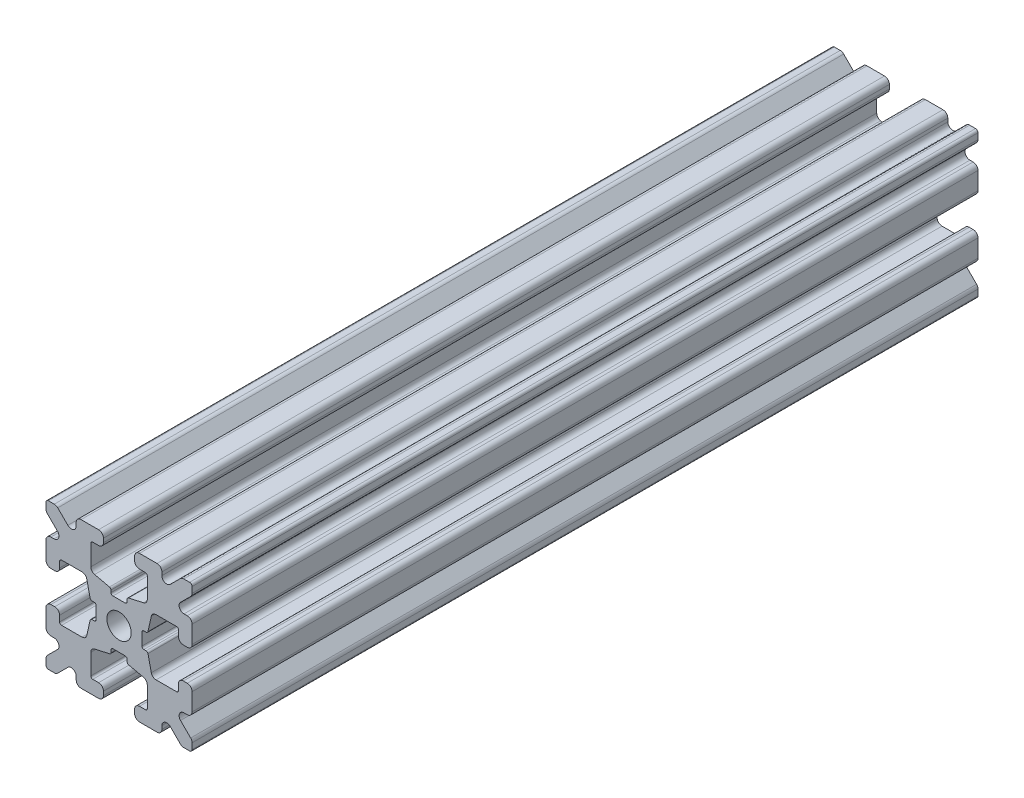
SolidWorks part; units mm, degrees
ref_plane "Front Plane" through (0, 0, 0) normal (0, 0, 1) x (1, 0, 0)
ref_plane "Top Plane" through (0, 0, 0) normal (0, 1, 0) x (1, 0, 0)
ref_plane "Right Plane" through (0, 0, 0) normal (1, 0, 0) x (0, 0, -1)
sketch "Sketch1" plane through (0, 0, 0) normal (0, 0, 1) x (1, 0, 0)
  line L1 (-7.5, -7.5) -> (7.5, -7.5)
  line L2 (-7.5, -7.5) -> (-7.5, 7.5)
  line L3 (-7.5, 7.5) -> (7.5, 7.5)
  line L4 (7.5, -7.5) -> (7.5, 7.5)
  line L5 (-7.5, -7.5) -> (7.5, 7.5) construction
  line L6 (-7.5, 7.5) -> (7.5, -7.5) construction
  circle A0 centre (0, 0) radius 1.25
  point P0 (0, 0)
  dimension "D2" = 2.5
  dimension "D1" = 15
extrude "Boss-Extrude1" add sketch "Sketch1" along normal mid plane 80.7
fillet "Fillet1" radius 0.25 4 edges at (7.5, -7.5, 0) (-7.5, -7.5, 0) (7.5, 7.5, 0) (-7.5, 7.5, 0)
sketch "Sketch2" plane through (0, 0, 40.35) normal (0, 0, 1) x (1, 0, 0)
  line L0 (-7.5, 7.25) -> (-7.5, -7.25) construction
  line L1 (-7.5, 1.6) -> (-6.1, 1.6)
  line L2 (-7.5, 1.6) -> (-7.5, -1.6)
  line L3 (-7.5, -1.6) -> (-6.1, -1.6)
  line L4 (-6.1, 1.6) -> (-6.1, 2.9)
  line L5 (0, 0) -> (-12.1036, 0) construction
  line L6 (-6.1, -2.9) -> (-3.4, -2.9)
  line L7 (0, 0) -> (-7.25, 7.25) construction
  line L8 (-6.1, 2.9) -> (-3.4, 2.9)
  line L9 (-3.4, -2.9) -> (-3.4, 2.9)
  line L10 (55, 0) -> (-55, 0) construction
  line L11 (-6.1, -2.9) -> (-6.1, -1.6)
  line L12 (2.9, 6.1) -> (1.6, 6.1)
  line L13 (2.9, 3.4) -> (-2.9, 3.4)
  line L14 (-2.9, 6.1) -> (-2.9, 3.4)
  line L15 (2.9, 6.1) -> (2.9, 3.4)
  line L16 (-1.6, 6.1) -> (-2.9, 6.1)
  line L17 (1.6, 7.5) -> (1.6, 6.1)
  line L18 (-1.6, 7.5) -> (1.6, 7.5)
  line L19 (-1.6, 7.5) -> (-1.6, 6.1)
  line L20 (-1.6, -7.5) -> (-1.6, -6.1)
  line L21 (-1.6, -7.5) -> (1.6, -7.5)
  line L22 (1.6, -7.5) -> (1.6, -6.1)
  line L23 (-1.6, -6.1) -> (-2.9, -6.1)
  line L24 (2.9, -6.1) -> (2.9, -3.4)
  line L25 (-2.9, -6.1) -> (-2.9, -3.4)
  line L26 (2.9, -3.4) -> (-2.9, -3.4)
  line L27 (2.9, -6.1) -> (1.6, -6.1)
  line L28 (6.1, -2.9) -> (6.1, -1.6)
  line L29 (3.4, -2.9) -> (3.4, 2.9)
  line L30 (6.1, 2.9) -> (3.4, 2.9)
  line L31 (6.1, -2.9) -> (3.4, -2.9)
  line L32 (6.1, 1.6) -> (6.1, 2.9)
  line L33 (7.5, -1.6) -> (6.1, -1.6)
  line L34 (7.5, 1.6) -> (7.5, -1.6)
  line L35 (7.5, 1.6) -> (6.1, 1.6)
  dimension "D1" = 3.2
  dimension "D2" = 5.8
  dimension "D3" = 1.4
  dimension "D4" = 2.7
extrude "Cut-Extrude1" cut sketch "Sketch2" against normal through all
sketch "Sketch4" plane through (0, 0, 40.35) normal (0, 0, 1) x (1, 0, 0)
  line L0 (-3.4, 2.9) -> (-2.75, 0)
  line L1 (55, 0) -> (-55, 0) construction
  line L2 (-2.75, 0) -> (-3.4, -2.9)
  line L3 (-3.4, -2.9) -> (-3.4, 2.9) construction
  line L4 (-3.4, 2.9) -> (-3.4, -2.9)
  line L5 (-2.9, 3.4) -> (0, 2.75)
  line L6 (0, 2.75) -> (2.9, 3.4)
  line L7 (2.9, 3.4) -> (-2.9, 3.4)
  line L8 (3.4, 2.9) -> (2.75, 0)
  line L9 (2.75, 0) -> (3.4, -2.9)
  line L10 (3.4, -2.9) -> (3.4, 2.9)
  line L11 (-2.9, -3.4) -> (0, -2.75)
  line L12 (0, -2.75) -> (2.9, -3.4)
  line L13 (2.9, -3.4) -> (-2.9, -3.4)
  circle A2 centre (0, 0) radius 2.75
  circle A3 centre (0, 0) radius 2.75 construction
  dimension "D1" = 1.5
extrude "Cut-Extrude3" cut sketch "Sketch4" against normal through all
fillet "Fillet3" radius 0.5 16 edges at (-6.1, -1.6, 0) (-7.5, -1.6, 0) (-6.1, 1.6, 0) (-7.5, 1.6, 0) (-1.6, -7.5, 0) (-1.6, -6.1, 0) (1.6, -7.5, 0) (1.6, -6.1, 0) (6.1, -1.6, 0) (7.5, -1.6, 0) (7.5, 1.6, 0) (6.1, 1.6, 0) (1.6, 7.5, 0) (1.6, 6.1, 0) (-1.6, 7.5, 0) (-1.6, 6.1, 0)
fillet "Fillet4" radius 0.5 8 edges at (-3.4, 2.9, 0) (-3.4, -2.9, 0) (2.9, -3.4, 0) (-2.9, -3.4, 0) (3.4, -2.9, 0) (3.4, 2.9, 0) (-2.9, 3.4, 0) (2.9, 3.4, 0)
fillet "Fillet5" radius 3 4 edges at (0, -2.75, 0) (2.75, 0, 0) (-2.75, 0, 0) (0, 2.75, 0)
fillet "Fillet6" radius 0.2 8 edges at (-2.9, -6.1, 0) (2.9, -6.1, 0) (6.1, -2.9, 0) (6.1, 2.9, 0) (2.9, 6.1, 0) (-2.9, 6.1, 0) (-6.1, -2.9, 0) (-6.1, 2.9, 0)
sketch "Sketch5" plane through (0, 0, 40.35) normal (0, 0, 1) x (1, 0, 0)
  line L0 (0, 0) -> (-7.25, 7.25) construction
  line L1 (-7.5, 6.4393) -> (-5.4607, 4.4)
  line L2 (-6.4393, 7.5) -> (-4.4, 5.4607)
  line L3 (-7.5, 4.4) -> (-5.4607, 4.4)
  line L4 (-3.8003, 2.9) -> (-5.9, 2.9) construction
  line L5 (0, 0) -> (-12.1819, 0) construction
  line L6 (-4.4, 7.5) -> (-4.4, 5.4607)
  line L7 (-2.9, 5.9) -> (-2.9, 3.8003) construction
  line L8 (-7.5, 6.4393) -> (-7.5, 4.4)
  line L9 (-7.5, 7.25) -> (-7.5, 2.1) construction
  line L10 (2.1, -7.5) -> (7.25, -7.5) construction
  line L11 (7.5, -7.25) -> (7.5, -2.1) construction
  line L12 (7.25, 7.5) -> (2.1, 7.5) construction
  line L13 (-2.1, 7.5) -> (-7.25, 7.5) construction
  line L14 (-4.4, 7.5) -> (-6.4393, 7.5)
  line L16 (55, 0) -> (-55, 0) construction
  line L17 (0, 0) -> (0, 10.993) construction
  line L18 (0, -54.6431) -> (0, 54.6431) construction
  line L20 (4.4, 7.5) -> (6.4393, 7.5)
  line L22 (7.5, 6.4393) -> (7.5, 4.4)
  line L23 (4.4, 7.5) -> (4.4, 5.4607)
  line L24 (7.5, 4.4) -> (5.4607, 4.4)
  line L25 (6.4393, 7.5) -> (4.4, 5.4607)
  line L26 (7.5, 6.4393) -> (5.4607, 4.4)
  line L27 (7.5, -6.4393) -> (5.4607, -4.4)
  line L28 (6.4393, -7.5) -> (4.4, -5.4607)
  line L29 (7.5, -4.4) -> (5.4607, -4.4)
  line L30 (4.4, -7.5) -> (4.4, -5.4607)
  line L31 (7.5, -6.4393) -> (7.5, -4.4)
  line L33 (4.4, -7.5) -> (6.4393, -7.5)
  line L36 (-4.4, -7.5) -> (-6.4393, -7.5)
  line L38 (-7.5, -6.4393) -> (-7.5, -4.4)
  line L39 (-4.4, -7.5) -> (-4.4, -5.4607)
  line L40 (-7.5, -4.4) -> (-5.4607, -4.4)
  line L41 (-6.4393, -7.5) -> (-4.4, -5.4607)
  line L42 (-7.5, -6.4393) -> (-5.4607, -4.4)
  dimension "D1" = 1.5
  dimension "D2" = 1.5
  dimension "D3" = 1.5
extrude "Cut-Extrude4" cut sketch "Sketch5" against normal through all
fillet "Fillet8" radius 0.5 24 edges at (-5.4607, 4.4, 0) (-7.5, 4.4, 0) (-5.4607, -4.4, 0) (-7.5, -4.4, 0) (-4.4, -7.5, 0) (-4.4, -5.4607, 0) (4.4, -7.5, 0) (4.4, -5.4607, 0) (5.4607, -4.4, 0) (7.5, -4.4, 0) (7.5, 4.4, 0) (5.4607, 4.4, 0) (4.4, 5.4607, 0) (4.4, 7.5, 0) (-4.4, 5.4607, 0) (-4.4, 7.5, 0) (-6.4393, 7.5, 0) (-7.5, 6.4393, 0) (6.4393, 7.5, 0) (7.5, 6.4393, 0) (6.4393, -7.5, 0) (7.5, -6.4393, 0) (-6.4393, -7.5, 0) (-7.5, -6.4393, 0)
sketch "Sketch6" plane through (0, 0, 40.35) normal (0, 0, 1) x (1, 0, 0)
  line L0 (0, 0) -> (0, 11.013) construction
  line L1 (0.6561, 2.8971) -> (2.1235, 2.8971) construction
  line L2 (0, -54.6431) -> (0, 54.6431) construction
  line L3 (0, 0) -> (7.25, 7.25) construction
  line L4 (7.5, 0.8255) -> (7.5, -0.8255)
  line L5 (2.3471, 0.8255) -> (7.5, 0.8255)
  line L6 (0, 0) -> (12.4016, 0) construction
  line L7 (0.8255, -7.5) -> (-0.8255, -7.5)
  line L8 (2.3471, -0.8255) -> (2.3471, 0.8255)
  line L9 (0.8255, -2.3471) -> (0.8255, -7.5)
  line L10 (7.5, -0.8255) -> (2.3471, -0.8255)
  line L11 (-7.5, -0.8255) -> (-2.3471, -0.8255)
  line L12 (-2.3471, -0.8255) -> (-2.3471, 0.8255)
  line L13 (-0.8255, -2.3471) -> (0.8255, -2.3471)
  line L14 (-0.8255, 7.5) -> (-0.8255, 2.3471)
  line L15 (-0.8255, 2.3471) -> (0.8255, 2.3471)
  line L16 (-0.8255, -7.5) -> (-0.8255, -2.3471)
  line L17 (0.8255, 2.3471) -> (0.8255, 7.5)
  line L18 (0.8255, 7.5) -> (-0.8255, 7.5)
  line L19 (3.9, 7.5) -> (2.1, 7.5) construction
  line L20 (-2.3471, 0.8255) -> (-7.5, 0.8255)
  line L21 (-7.5, 0.8255) -> (-7.5, -0.8255)
  point P5 (0, -2.5973)
  point P7 (0, 2.5973)
  dimension "D3" = 0.55
  dimension "D1" = 1.651
extrude "Cut-Extrude5" cut sketch "Sketch6" against normal through all
fillet "Fillet10" radius 0.2 16 edges at (-2.935, 0.8255, 0) (-2.935, -0.8255, 0) (2.935, -0.8255, 0) (2.935, 0.8255, 0) (0.8255, 2.935, 0) (-0.8255, 2.935, 0) (-2.3471, 0.8255, 0) (-2.3471, -0.8255, 0) (0.8255, 2.3471, 0) (-0.8255, 2.3471, 0) (2.3471, 0.8255, 0) (2.3471, -0.8255, 0) (0.8255, -2.935, 0) (0.8255, -2.3471, 0) (-0.8255, -2.3471, 0) (-0.8255, -2.935, 0)
